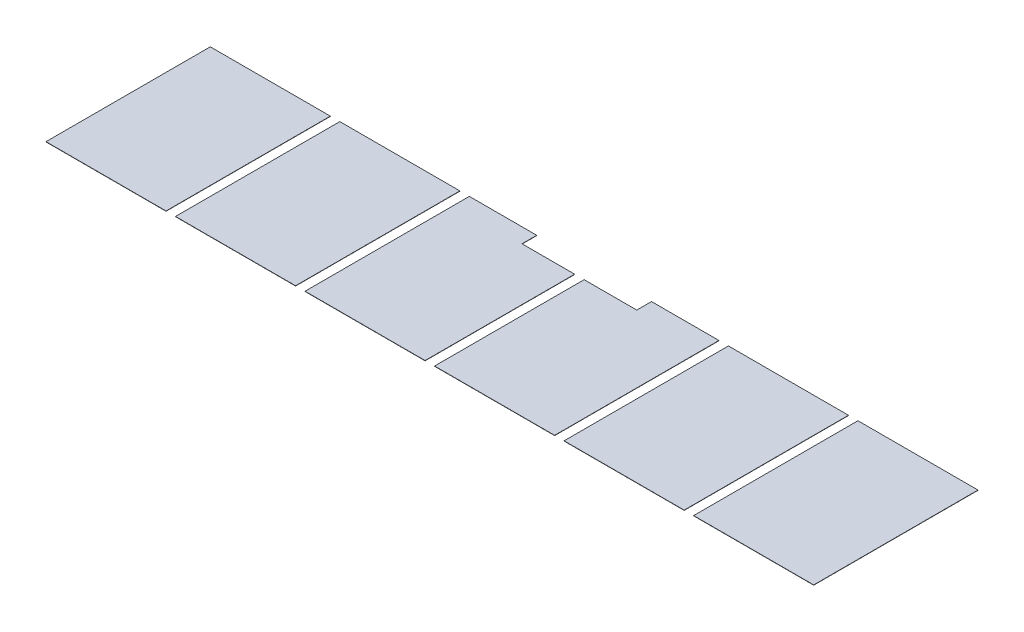
SolidWorks part; units mm, degrees
ref_plane "Front Plane" through (0, 0, 0) normal (0, 0, 1) x (1, 0, 0)
ref_plane "Top Plane" through (0, 0, 0) normal (0, 1, 0) x (1, 0, 0)
ref_plane "Right Plane" through (0, 0, 0) normal (1, 0, 0) x (0, 0, -1)
ref_plane "Insulated Subfloor Plane" through (0, 40.64, 0) normal (0, 1, 0) x (1, 0, 0)
sketch "Sketch1" plane through (0, 40.64, 0) normal (0, 1, 0) x (1, 0, 0)
  line L4 (3073.4, 2044.7) -> (1625.6, 2044.7)
  line L5 (1625.6, 2044.7) -> (1625.6, 63.5)
  line L6 (1625.6, 63.5) -> (3073.4, 63.5)
  line L7 (3073.4, 63.5) -> (3073.4, 2044.7)
  line L8 (3073.4, 2044.7) -> (1625.6, 2044.7)
  line L9 (1625.6, 2044.7) -> (1625.6, 63.5)
  line L10 (1625.6, 63.5) -> (3073.4, 63.5)
  line L11 (3073.4, 63.5) -> (3073.4, 2044.7)
  line L12 (1511.3, 2044.7) -> (63.5, 2044.7)
  line L13 (63.5, 2044.7) -> (63.5, 63.5)
  line L14 (63.5, 63.5) -> (1511.3, 63.5)
  line L15 (1511.3, 63.5) -> (1511.3, 2044.7)
  line L16 (1511.3, 2044.7) -> (63.5, 2044.7)
  line L17 (63.5, 2044.7) -> (63.5, 63.5)
  line L18 (63.5, 63.5) -> (1511.3, 63.5)
  line L19 (1511.3, 63.5) -> (1511.3, 2044.7)
  line L20 (9321.8, 2044.7) -> (7874, 2044.7)
  line L21 (7874, 2044.7) -> (7874, 63.5)
  line L22 (7874, 63.5) -> (9321.8, 63.5)
  line L23 (9321.8, 63.5) -> (9321.8, 2044.7)
  line L24 (9321.8, 2044.7) -> (7874, 2044.7)
  line L25 (7874, 2044.7) -> (7874, 63.5)
  line L26 (7874, 63.5) -> (9321.8, 63.5)
  line L27 (9321.8, 63.5) -> (9321.8, 2044.7)
  line L28 (7759.7, 63.5) -> (7759.7, 2044.7)
  line L29 (6311.9, 63.5) -> (7759.7, 63.5)
  line L30 (6311.9, 2044.7) -> (6311.9, 63.5)
  line L31 (7759.7, 2044.7) -> (6311.9, 2044.7)
  line L32 (7759.7, 63.5) -> (7759.7, 2044.7)
  line L33 (6311.9, 63.5) -> (7759.7, 63.5)
  line L34 (6311.9, 2044.7) -> (6311.9, 63.5)
  line L35 (7759.7, 2044.7) -> (6311.9, 2044.7)
  line L38 (6197.6, 2044.7) -> (5384.8, 2044.7)
  line L39 (6197.6, 63.5) -> (6197.6, 2044.7)
  line L40 (4749.8, 63.5) -> (6197.6, 63.5)
  line L41 (4749.8, 1866.9) -> (4749.8, 63.5)
  line L42 (5384.8, 1866.9) -> (4749.8, 1866.9)
  line L43 (5384.8, 2044.7) -> (5384.8, 1866.9)
  line L44 (6197.6, 2044.7) -> (5384.8, 2044.7)
  line L45 (6197.6, 63.5) -> (6197.6, 2044.7)
  line L46 (4749.8, 63.5) -> (6197.6, 63.5)
  line L47 (4749.8, 1866.9) -> (4749.8, 63.5)
  line L48 (5384.8, 1866.9) -> (4749.8, 1866.9)
  line L49 (5384.8, 2044.7) -> (5384.8, 1866.9)
  line L50 (3187.7, 2044.7) -> (3187.7, 63.5)
  line L51 (4000.5, 2044.7) -> (3187.7, 2044.7)
  line L52 (4000.5, 1866.9) -> (4000.5, 2044.7)
  line L53 (4635.5, 1866.9) -> (4000.5, 1866.9)
  line L54 (4635.5, 63.5) -> (4635.5, 1866.9)
  line L55 (3187.7, 63.5) -> (4635.5, 63.5)
  line L56 (3187.7, 2044.7) -> (3187.7, 63.5)
  line L57 (4000.5, 2044.7) -> (3187.7, 2044.7)
  line L58 (4000.5, 1866.9) -> (4000.5, 2044.7)
  line L59 (4635.5, 1866.9) -> (4000.5, 1866.9)
  line L60 (4635.5, 63.5) -> (4635.5, 1866.9)
  line L61 (3187.7, 63.5) -> (4635.5, 63.5)
  dimension "D1" = 0
  dimension "D2" = 0
  dimension "D3" = 0
  dimension "D4" = 0
  dimension "D5" = 0
  dimension "D6" = 0
extrude "Boss-Extrude3" add sketch "Sketch1" along normal up to surface (3.175 mm away)
